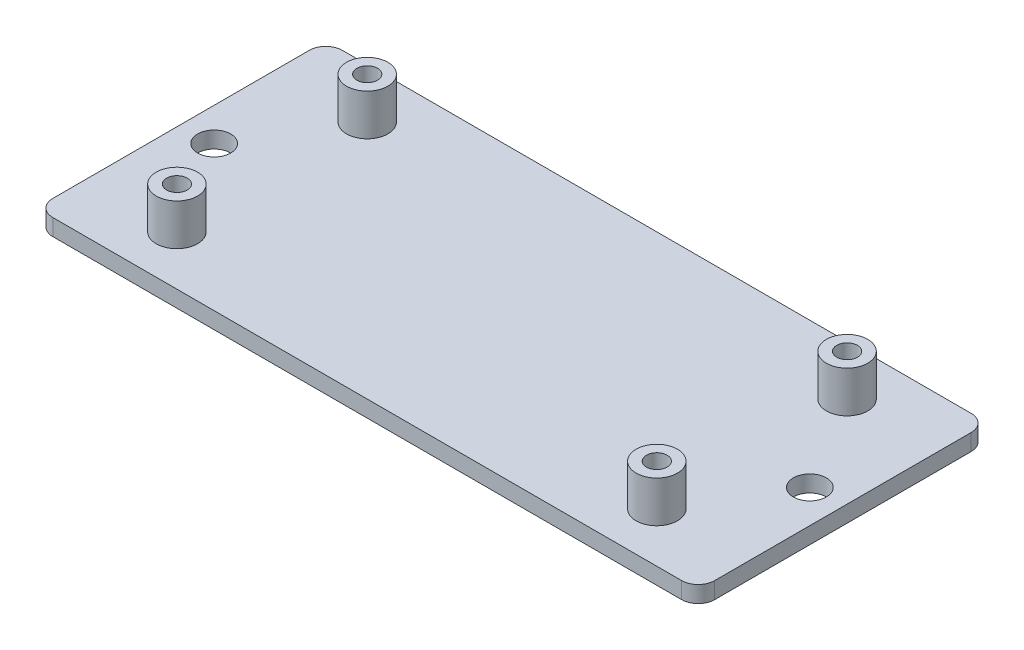
SolidWorks part; units mm, degrees
ref_plane "Спереди" through (0, 0, 0) normal (0, 0, 1) x (1, 0, 0)
ref_plane "Сверху" through (0, 0, 0) normal (0, 1, 0) x (1, 0, 0)
ref_plane "Справа" through (0, 0, 0) normal (1, 0, 0) x (0, 0, -1)
sketch "Эскиз1" plane through (0, 0, 0) normal (0, 1, 0) x (1, 0, 0)
  line L1 (0, 0) -> (80, 0)
  line L2 (0, 0) -> (0, -35)
  line L3 (0, -35) -> (80, -35)
  line L4 (80, 0) -> (80, -35)
  dimension "D1" = 80
  dimension "D2" = 35
extrude "Бобышка-Вытянуть1" add sketch "Эскиз1" along normal blind 2
sketch "Эскиз2" plane through (0, 2, 0) normal (0, 1, 0) x (1, 0, 0)
  line L0 (0, 0) -> (0, -35) construction
  line L1 (80, -35) -> (80, 0) construction
  line L2 (80, 0) -> (0, 0) construction
  line L3 (0, -35) -> (80, -35) construction
  circle A0 centre (11, -6) radius 2.5
  circle A1 centre (11, -29) radius 2.5
  circle A2 centre (69, -6) radius 2.5
  circle A3 centre (69, -29) radius 2.5
  dimension "D1" = 11
  dimension "D2" = 11
  dimension "D3" = 11
  dimension "D4" = 11
  dimension "D5" = 6
  dimension "D6" = 6
  dimension "D7" = 5
  dimension "D8" = 6
  dimension "D9" = 6
  dimension "D10" = 5
  dimension "D11" = 5
  dimension "D12" = 5
extrude "Бобышка-Вытянуть2" add sketch "Эскиз2" along normal blind 5
sketch "Эскиз3" plane through (0, 7, 0) normal (0, 1, 0) x (1, 0, 0)
  circle A0 centre (11, -6) radius 1.25
  circle A1 centre (11, -29) radius 1.25
  circle A2 centre (69, -6) radius 1.25
  circle A3 centre (69, -29) radius 1.25
  dimension "D1" = 2.5
  dimension "D2" = 2.5
  dimension "D3" = 2.5
  dimension "D4" = 2.5
extrude "Вырез-Вытянуть1" cut sketch "Эскиз3" against normal through all both and the other way through all
sketch "Эскиз4" plane through (0, 2, 0) normal (0, 1, 0) x (1, 0, 0)
  line L0 (0, -17.5) -> (80, -17.5) construction
  line L1 (0, 0) -> (0, -35) construction
  line L2 (80, -35) -> (80, 0) construction
  circle A0 centre (4, -17.5) radius 2
  circle A1 centre (76, -17.5) radius 2
  dimension "D2" = 4
  dimension "D3" = 4
  dimension "D4" = 4
  dimension "D1" = 4
extrude "Вырез-Вытянуть2" cut sketch "Эскиз4" against normal through all
fillet "Скругление1" radius 2 1 edges at (0, 1, 0) type face fillet first side face at (0, 1, 17.5) second side face at (40, 1, 0)
fillet "Скругление2" radius 2 1 edges at (0, 1, 35) type face fillet first side face at (0, 1, 18.5) second side face at (40, 1, 35)
fillet "Скругление3" radius 2 1 edges at (80, 1, 35) type face fillet first side face at (41, 1, 35) second side face at (80, 1, 17.5)
fillet "Скругление4" radius 2 1 edges at (80, 1, 0) type face fillet first side face at (41, 1, 0) second side face at (80, 1, 16.5)
